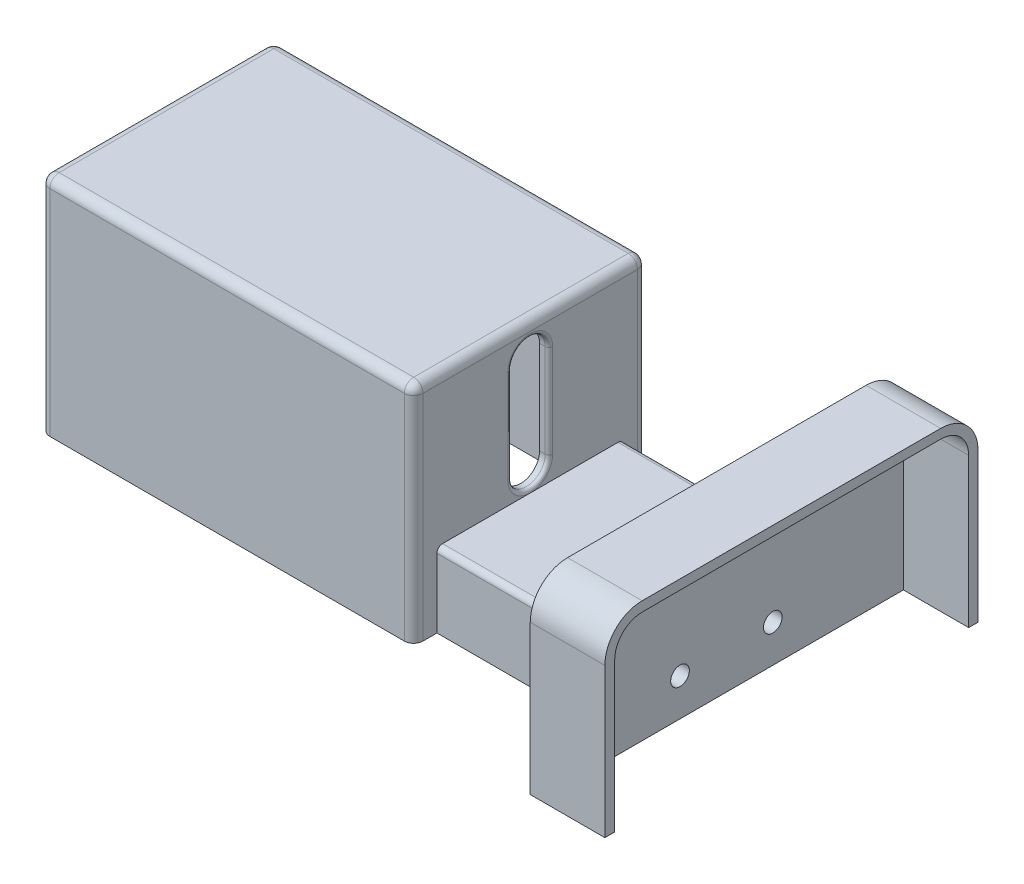
SolidWorks part; units mm, degrees
ref_plane "Front Plane" through (0, 0, 0) normal (0, 0, 1) x (1, 0, 0)
ref_plane "Top Plane" through (0, 0, 0) normal (0, 1, 0) x (1, 0, 0)
ref_plane "Right Plane" through (0, 0, 0) normal (1, 0, 0) x (0, 0, -1)
sketch "Sketch1" plane through (0, 0, 0) normal (0, 1, 0) x (1, 0, 0)
  line L1 (-91.2215, 44.4444) -> (108.7785, 44.4444)
  line L2 (-91.2215, 44.4444) -> (-91.2215, -80.5556)
  line L3 (-91.2215, -80.5556) -> (108.7785, -80.5556)
  line L4 (108.7785, 44.4444) -> (108.7785, -80.5556)
  dimension "D1" = 200
  dimension "D2" = 125
extrude "Boss-Extrude1" add sketch "Sketch1" along normal blind 120
sketch "Sketch2" plane through (0, 120, 0) normal (0, 1, 0) x (1, 0, 0)
  line L0 (-91.2215, 44.4444) -> (-91.2215, -80.5556) construction
  line L1 (108.7785, 44.4444) -> (-91.2215, 44.4444) construction
  line L2 (-91.2215, -80.5556) -> (108.7785, -80.5556) construction
  line L3 (108.7785, -80.5556) -> (108.7785, 44.4444) construction
  line L4 (-86.2215, 44.4444) -> (103.7785, 44.4444)
  line L5 (108.7785, 39.4444) -> (108.7785, -75.5556)
  line L6 (-86.2215, -80.5556) -> (103.7785, -80.5556)
  line L7 (-91.2215, 39.4444) -> (-91.2215, -75.5556)
  arc A0 (-86.2215, 44.4444) -> (-91.2215, 39.4444) centre (-86.2215, 39.4444) ccw
  arc A1 (-91.2215, -75.5556) -> (-86.2215, -80.5556) centre (-86.2215, -75.5556) ccw
  arc A2 (108.7785, -75.5556) -> (103.7785, -80.5556) centre (103.7785, -75.5556) cw
  arc A3 (108.7785, 39.4444) -> (103.7785, 44.4444) centre (103.7785, 39.4444) ccw
  point P0 (-86.2215, 39.4444)
  point P1 (103.7785, 39.4444)
  point P2 (-86.2215, -75.5556)
  point P3 (103.7785, -75.5556)
  dimension "D1" = 5
  dimension "D2" = 115
  dimension "D3" = 5
  dimension "D4" = 190
  dimension "D5" = 190
  dimension "D6" = 115
  dimension "D7" = 0
  dimension "D8" = 5
extrude "Boss-Extrude2" add sketch "Sketch2" along normal blind 120
sketch "Sketch3" plane through (0, 0, 0) normal (0, -1, 0) x (-1, 0, 0)
  line L1 (91.2215, -80.5556) -> (-108.7785, -80.5556)
  line L2 (91.2215, -80.5556) -> (91.2215, 44.4444)
  line L3 (91.2215, 44.4444) -> (-108.7785, 44.4444)
  line L4 (-108.7785, -80.5556) -> (-108.7785, 44.4444)
extrude "Cut-Extrude1" cut sketch "Sketch3" against normal blind 120
fillet "Fillet1" radius 5 8 edges at (-89.757, 240, 79.0911) (-91.2215, 240, 18.0556) (-89.757, 240, -42.98) (8.7785, 240, -44.4444) (107.3141, 240, -42.98) (108.7785, 240, 18.0556) (107.3141, 240, 79.0911) (8.7785, 240, 80.5556)
sketch "Sketch4" plane through (108.7785, 0, 0) normal (1, 0, 0) x (0, 0, -1)
  line L0 (39.4444, 120) -> (-75.5556, 120) construction
  line L1 (-68.0556, 160) -> (31.9444, 160)
  line L2 (-68.0556, 160) -> (-68.0556, 120)
  line L3 (-68.0556, 120) -> (31.9444, 120)
  line L4 (31.9444, 160) -> (31.9444, 120)
  line L5 (-75.5556, 235) -> (-75.5556, 120) construction
  dimension "D1" = 7.5
  dimension "D2" = 100
  dimension "D3" = 40
extrude "Boss-Extrude3" add sketch "Sketch4" along normal blind 100
fillet "Fillet3" radius 3 2 edges at (158.7785, 160, 68.0556) (158.7785, 160, -31.9444)
sketch "Sketch5" plane through (0, 120, 0) normal (0, -1, 0) x (-1, 0, 0)
  line L1 (86.2215, -75.5556) -> (-103.7785, -75.5556)
  line L2 (86.2215, -75.5556) -> (86.2215, 39.4444)
  line L3 (86.2215, 39.4444) -> (-103.7785, 39.4444)
  line L4 (-103.7785, -75.5556) -> (-103.7785, 39.4444)
  point P0 (86.2215, -75.5556)
  point P1 (-103.7785, 39.4444)
extrude "Cut-Extrude2" cut sketch "Sketch5" against normal blind 115
sketch "Sketch6" plane through (0, 235, 0) normal (0, -1, 0) x (-1, 0, 0)
  line L0 (-103.7785, -75.5556) -> (86.2215, -75.5556) construction
  line L1 (86.2215, -75.5556) -> (71.2215, -75.5556)
  line L2 (86.2215, -75.5556) -> (86.2215, -60.5556)
  line L3 (86.2215, -60.5556) -> (71.2215, -60.5556)
  line L4 (71.2215, -75.5556) -> (71.2215, -60.5556)
  line L5 (-88.7785, -75.5556) -> (-103.7785, -75.5556)
  line L6 (-88.7785, -75.5556) -> (-88.7785, -60.5556)
  line L7 (-88.7785, -60.5556) -> (-103.7785, -60.5556)
  line L8 (-103.7785, -75.5556) -> (-103.7785, -60.5556)
  line L9 (-103.7785, 39.4444) -> (-103.7785, -75.5556) construction
  line L11 (-103.7785, 39.4444) -> (-88.7785, 39.4444)
  line L12 (-103.7785, 39.4444) -> (-103.7785, 24.4444)
  line L13 (-103.7785, 24.4444) -> (-88.7785, 24.4444)
  line L14 (-88.7785, 39.4444) -> (-88.7785, 24.4444)
  line L15 (86.2215, 39.4444) -> (71.2215, 39.4444)
  line L16 (86.2215, 39.4444) -> (86.2215, 24.4444)
  line L17 (86.2215, 24.4444) -> (71.2215, 24.4444)
  line L18 (71.2215, 39.4444) -> (71.2215, 24.4444)
  dimension "D1" = 160
  dimension "D2" = 15
  dimension "D3" = 15
  dimension "D4" = 85
  dimension "D5" = 160
  dimension "D6" = 15
  dimension "D7" = 85
extrude "Boss-Extrude4" add sketch "Sketch6" along normal blind 110
sketch "Sketch7" plane through (208.7785, 0, 0) normal (1, 0, 0) x (0, 0, -1)
  line L0 (-80.5556, 235) -> (-80.5556, 120) construction
  line L1 (-118.0556, 220) -> (81.9444, 220)
  line L2 (-118.0556, 220) -> (-118.0556, 120)
  line L3 (-118.0556, 120) -> (81.9444, 120)
  line L4 (81.9444, 220) -> (81.9444, 120)
  line L5 (-68.0556, 120) -> (31.9444, 120) construction
  dimension "D1" = 200
  dimension "D2" = 37.5
  dimension "D3" = 0
  dimension "D4" = 100
extrude "Boss-Extrude5" add sketch "Sketch7" along normal blind 40
fillet "Fillet4" radius 20 2 edges at (228.7785, 220, -81.9444) (228.7785, 220, 118.0556)
sketch "Sketch9" plane through (248.7785, 0, 0) normal (1, 0, 0) x (0, 0, -1)
  line L0 (-113.0556, 120) -> (-113.0556, 200)
  line L1 (-118.0556, 120) -> (81.9444, 120) construction
  line L3 (76.9444, 200) -> (76.9444, 120)
  line L4 (76.9444, 120) -> (-113.0556, 120)
  line L5 (-98.0556, 214.7242) -> (61.9444, 215)
  line L7 (-112.7798, 200) -> (76.9444, 200)
  line L8 (-112.7798, 200) -> (-112.7798, 120)
  arc A0 (-98.0556, 214.7242) -> (-112.7798, 200) centre (-98.0556, 200) ccw
  arc A1 (76.9444, 200) -> (61.9444, 215) centre (61.9444, 200) ccw
  dimension "D1" = 190
  dimension "D2" = 5
  dimension "D3" = 80
extrude "Cut-Extrude9" cut sketch "Sketch9" against normal blind 35 contours L7 L8 L4 L3 region at (248.7785, 160, 17.9177)
extrude "Cut-Extrude10" cut sketch "Sketch9<3>" against normal blind 35 contours L7 A1 L5 A0 region at (248.7785, 207.2883, 17.6283)
sketch "Sketch9<3>" plane through (248.7785, 0, 0) normal (1, 0, 0) x (0, 0, -1) same geometry as "Sketch9"
sketch "Sketch10" plane through (108.7785, 0, 0) normal (1, 0, 0) x (0, 0, -1)
  line L0 (39.4444, 235) -> (39.4444, 120) construction
  line L2 (-28.0556, 222) -> (-28.0556, 172)
  line L4 (-8.0556, 222) -> (-8.0556, 172)
  line L5 (39.4444, 120) -> (-75.5556, 120) construction
  arc A0 (-8.0556, 172) -> (-28.0556, 172) centre (-18.0556, 172) cw
  arc A1 (-8.0556, 222) -> (-28.0556, 222) centre (-18.0556, 222) ccw
  dimension "D1" = 50
  dimension "D2" = 47.5
  dimension "D3" = 20
  dimension "D4" = 52
extrude "Cut-Extrude11" cut sketch "Sketch10" against normal blind 20
fillet "Fillet5" radius 2 4 edges at (108.7785, 197, 28.0556) (108.7785, 232, 18.0556) (108.7785, 162, 18.0556) (108.7785, 197, 8.0556)
sketch "Sketch11" plane through (213.7785, 0, 0) normal (1, 0, 0) x (0, 0, -1)
  line L0 (-112.7798, 200) -> (-112.7798, 120) construction
  line L1 (76.9444, 200) -> (76.9444, 120) construction
  line L2 (-112.7798, 120) -> (76.9444, 120) construction
  circle A0 centre (-42.7798, 140) radius 5
  circle A1 centre (6.9444, 140) radius 5
  dimension "D3" = 10
  dimension "D4" = 10
  dimension "D1" = 70
  dimension "D2" = 70
  dimension "D5" = 20
  dimension "D6" = 20
extrude "Cut-Extrude12" cut sketch "Sketch11" against normal blind 132
